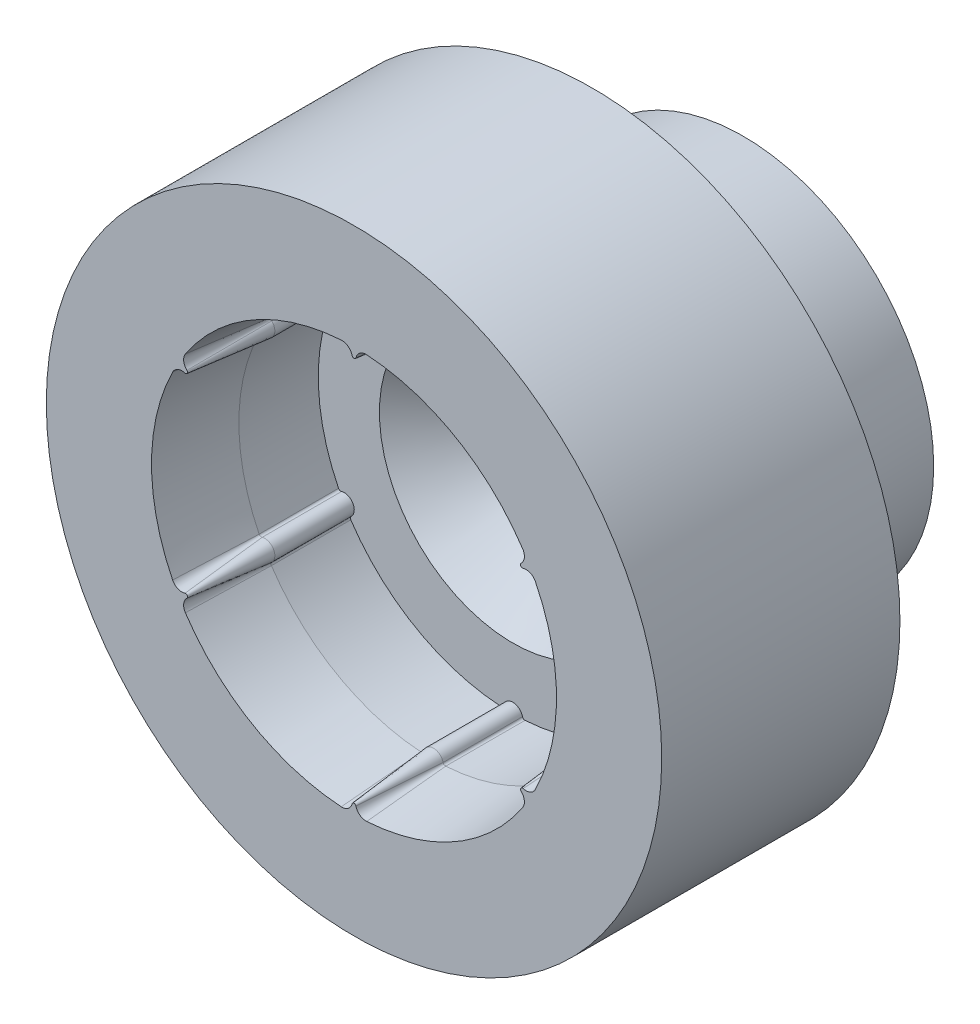
SolidWorks part; units mm, degrees
material "PET"
ref_plane "Front Plane" through (0, 0, 0) normal (0, 0, 1) x (1, 0, 0)
ref_plane "Top Plane" through (0, 0, 0) normal (0, 1, 0) x (1, 0, 0)
ref_plane "Right Plane" through (0, 0, 0) normal (1, 0, 0) x (0, 0, -1)
sketch "Sketch1" plane through (0, 0, 0) normal (0, 0, 1) x (1, 0, 0)
  circle A0 centre (0, 0) radius 0.5
  circle A1 centre (0, 0) radius 4.9
  circle A2 centre (0, 0) radius 7.75
  circle A3 centre (0, 4.9) radius 0.25
  circle A4 centre (-0.3041, 4.8279) radius 0.0625
  circle A5 centre (0.3041, 4.8279) radius 0.0625
  dimension "D1" = 9.8
  dimension "D2" = 15.5
  dimension "D3" = 1
  dimension "D4" = 0.5
  dimension "D5" = 0.125
extrude "Boss-Extrude1" add sketch "Sketch1" along normal blind 2 contours A1 A0 | A0 | A1 A3 | A5 | A5 A1 A3 | A4 | A4 A3 A1 region at (0, 0, 0) region at (-3.2593, -3.4711, 0) region at (0.2622, 4.8815, 0) region at (0.3041, 4.8279, 0) region at (-0.2622, 4.8815, 0) region at (-0.3041, 4.8279, 0) region at (0, 4.7928, 0)
extrude "Boss-Extrude2" add sketch "Sketch1<3>" along normal blind 6 contours A2 A1 | A1 A3 region at (0, 5.0049, 0) region at (-7.5308, 0, 0)
sketch "Sketch1<3>" plane through (0, 0, 0) normal (0, 0, 1) x (1, 0, 0) same geometry as "Sketch1"
extrude "Boss-Extrude3" add sketch "Sketch1<4>" against normal blind 3.8 contours A1
sketch "Sketch1<4>" plane through (0, 0, 0) normal (0, 0, 1) x (1, 0, 0) same geometry as "Sketch1"
hole_wizard "CSK for  SFHCS1" positions "Sketch3" profile "Sketch4" countersink size "M3" standard "ANSI Metric" end condition through all
sketch "Sketch3" plane through (0, 0, 2) normal (0, 0, 1) x (1, 0, 0)
  point P0 (0, 0)
sketch "Sketch4" plane through (0, 0, 2) normal (1, 0, 0) x (0, -1, 0)
  line L0 (0, 0) -> (0, 5.8)
  line L1 (0, 5.8) -> (1.6, 5.8)
  line L2 (1.6, 5.8) -> (1.6, 1.76)
  line L3 (1.6, 1.76) -> (3.36, 0)
  line L5 (3.36, 0) -> (0, 0)
  line L6 (-1.6, 1.76) -> (-3.36, 0) construction
  line L11 (0, -6.35) -> (0, 107.95) construction
  dimension "Thru Hole Dia." = 3.2
  dimension "Thru Hole Depth" = 5.8
  dimension "Near C'Sink Dia." = 6.72
  dimension "Near C'Sink Angle" = 90
extrude "Boss-Extrude4" add sketch "Sketch1<5>" along normal up to surface (6 mm away) contours A1 A3 | A1 A3 | A5 A1 A3 | A4 A3 A1 region at (0.2622, 4.8815, 0) region at (-0.2622, 4.8815, 0) region at (0, 4.7928, 0) region at (0, 5.0049, 0) up to face at (4.9, 0, 6)
sketch "Sketch1<5>" plane through (0, 0, 0) normal (0, 0, 1) x (1, 0, 0) same geometry as "Sketch1"
pattern_circular "CirPattern1" count 6 over 360 about axis through (0, 0, 2) along (0, 0, 1) of "Boss-Extrude4"
chamfer "Chamfer2" distance 0.2 distance2 2 1 edges at (-4.9, 0, 6) first distance on face at (0, 0, 6)
sketch "Sketch5" plane through (0, 0, 6) normal (0, 0, 1) x (1, 0, 0)
  circle A0 centre (0, 0) radius 4.85
  circle A1 centre (0, 0) radius 7.75
  circle A2 centre (0, 0) radius 7.75
  arc A5 (4.5683, 2.2673) -> (4.2579, 2.4021) centre (4.3332, 2.1506) ccw
  arc A17 (4.5683, -2.2673) -> (4.5683, 2.2673) centre (0, 0) ccw
  arc A18 (4.5683, -2.2673) -> (4.5683, 2.2673) centre (0, 0) ccw
  arc A49 (4.5683, 2.2673) -> (4.2579, 2.4021) centre (4.3332, 2.1506) ccw
  arc A50 (4.2579, -2.4021) -> (4.5683, -2.2673) centre (4.3332, -2.1506) ccw
  arc A53 (4.2579, -2.4021) -> (4.5683, -2.2673) centre (4.3332, -2.1506) ccw
  arc A57 (4.2579, -2.4021) -> (4.2092, -2.4864) centre (4.2435, -2.45) ccw
  arc A61 (4.2579, -2.4021) -> (4.2092, -2.4864) centre (4.2435, -2.45) ccw
  arc A65 (4.2477, -2.8226) -> (4.2092, -2.4864) centre (4.0291, -2.6773) ccw
  arc A69 (4.2477, -2.8226) -> (4.2092, -2.4864) centre (4.0291, -2.6773) ccw
  arc A73 (0.3206, -5.0899) -> (4.2477, -2.8226) centre (0, 0) ccw
  arc A77 (0.3206, -5.0899) -> (4.2477, -2.8226) centre (0, 0) ccw
  arc A81 (0.0487, -4.8885) -> (0.3206, -5.0899) centre (0.3041, -4.8279) ccw
  arc A83 (0.0487, -4.8885) -> (0.3206, -5.0899) centre (0.3041, -4.8279) ccw
  arc A85 (0.0487, -4.8885) -> (-0.0487, -4.8885) centre (0, -4.9) ccw
  arc A87 (0.0487, -4.8885) -> (-0.0487, -4.8885) centre (0, -4.9) ccw
  arc A89 (-0.3206, -5.0899) -> (-0.0487, -4.8885) centre (-0.3041, -4.8279) ccw
  arc A91 (-0.3206, -5.0899) -> (-0.0487, -4.8885) centre (-0.3041, -4.8279) ccw
  arc A93 (-4.2477, -2.8226) -> (-0.3206, -5.0899) centre (0, 0) ccw
  arc A95 (-4.2477, -2.8226) -> (-0.3206, -5.0899) centre (0, 0) ccw
  arc A97 (-4.2092, -2.4864) -> (-4.2477, -2.8226) centre (-4.0291, -2.6773) ccw
  arc A99 (-4.2092, -2.4864) -> (-4.2477, -2.8226) centre (-4.0291, -2.6773) ccw
  arc A101 (-4.2092, -2.4864) -> (-4.2579, -2.4021) centre (-4.2435, -2.45) ccw
  arc A103 (-4.2092, -2.4864) -> (-4.2579, -2.4021) centre (-4.2435, -2.45) ccw
  arc A105 (-4.5683, -2.2673) -> (-4.2579, -2.4021) centre (-4.3332, -2.1506) ccw
  arc A106 (-4.5683, -2.2673) -> (-4.2579, -2.4021) centre (-4.3332, -2.1506) ccw
  arc A107 (-4.5683, 2.2673) -> (-4.5683, -2.2673) centre (0, 0) ccw
  arc A108 (-4.5683, 2.2673) -> (-4.5683, -2.2673) centre (0, 0) ccw
  arc A109 (-4.2579, 2.4021) -> (-4.5683, 2.2673) centre (-4.3332, 2.1506) ccw
  arc A110 (-4.2579, 2.4021) -> (-4.5683, 2.2673) centre (-4.3332, 2.1506) ccw
  arc A111 (-4.2579, 2.4021) -> (-4.2092, 2.4864) centre (-4.2435, 2.45) ccw
  arc A112 (-4.2579, 2.4021) -> (-4.2092, 2.4864) centre (-4.2435, 2.45) ccw
  arc A113 (-4.2477, 2.8226) -> (-4.2092, 2.4864) centre (-4.0291, 2.6773) ccw
  arc A114 (-4.2477, 2.8226) -> (-4.2092, 2.4864) centre (-4.0291, 2.6773) ccw
  arc A115 (-0.3206, 5.0899) -> (-4.2477, 2.8226) centre (0, 0) ccw
  arc A116 (-0.3206, 5.0899) -> (-4.2477, 2.8226) centre (0, 0) ccw
  arc A117 (-0.0487, 4.8885) -> (-0.3206, 5.0899) centre (-0.3041, 4.8279) ccw
  arc A118 (-0.0487, 4.8885) -> (-0.3206, 5.0899) centre (-0.3041, 4.8279) ccw
  arc A119 (-0.0487, 4.8885) -> (0.0487, 4.8885) centre (0, 4.9) ccw
  arc A120 (-0.0487, 4.8885) -> (0.0487, 4.8885) centre (0, 4.9) ccw
  arc A121 (0.3206, 5.0899) -> (0.0487, 4.8885) centre (0.3041, 4.8279) ccw
  arc A122 (0.3206, 5.0899) -> (0.0487, 4.8885) centre (0.3041, 4.8279) ccw
  arc A123 (4.2477, 2.8226) -> (0.3206, 5.0899) centre (0, 0) ccw
  arc A124 (4.2477, 2.8226) -> (0.3206, 5.0899) centre (0, 0) ccw
  arc A125 (4.2092, 2.4864) -> (4.2477, 2.8226) centre (4.0291, 2.6773) ccw
  arc A126 (4.2092, 2.4864) -> (4.2477, 2.8226) centre (4.0291, 2.6773) ccw
  arc A127 (4.2092, 2.4864) -> (4.2579, 2.4021) centre (4.2435, 2.45) ccw
  arc A128 (4.2092, 2.4864) -> (4.2579, 2.4021) centre (4.2435, 2.45) ccw
  dimension "D3" = 9.7
  dimension "D1" = 0
  dimension "D2" = 0
chamfer "Chamfer3" distance 0.1 distance2 2.5 1 edges at (4.9, 0, -3.8) first distance on face at (1.6, 0, -3.8)
sketch "Sketch6" [suppressed] plane through (0, 0, 2) normal (0, 0, 1) x (1, 0, 0)
  circle A0 centre (0, 0) radius 4.9
  circle A1 centre (0, 0) radius 7.5
  circle A2 centre (0, 0) radius 7.5
  dimension "D2" = 9.8
  dimension "D1" = 0
extrude "Boss-Extrude5" [suppressed] add sketch "Sketch6" along normal up to surface (4 mm away)
sketch "Sketch7" [suppressed] plane through (0, 0, 6) normal (0, 0, 1) x (1, 0, 0)
  circle A0 centre (0, 0) radius 4.9 construction
  circle A1 centre (0, 0) radius 4.9
  circle A2 centre (0, 4.9) radius 0.25
  circle A3 centre (-0.3041, 4.8279) radius 0.0625
  circle A4 centre (0.3041, 4.8279) radius 0.0625
  circle A5 centre (0, 7.5) radius 0.25 construction
  circle A6 centre (0, 7.5) radius 0.25 construction
  circle A7 centre (0.3048, 7.4312) radius 0.0625 construction
extrude "Boss-Extrude6" [suppressed] add sketch "Sketch7" against normal up to surface (4 mm away)
pattern_circular "CirPattern2" [suppressed] count 6 over 360 of bodies 108
chamfer "Chamfer4" [suppressed] distance 0.1 distance2 2
chamfer "Chamfer5" [suppressed] distance 3 angle 45
equation "\"D5@Sketch1\"=\"D4@Sketch1\"/4"
